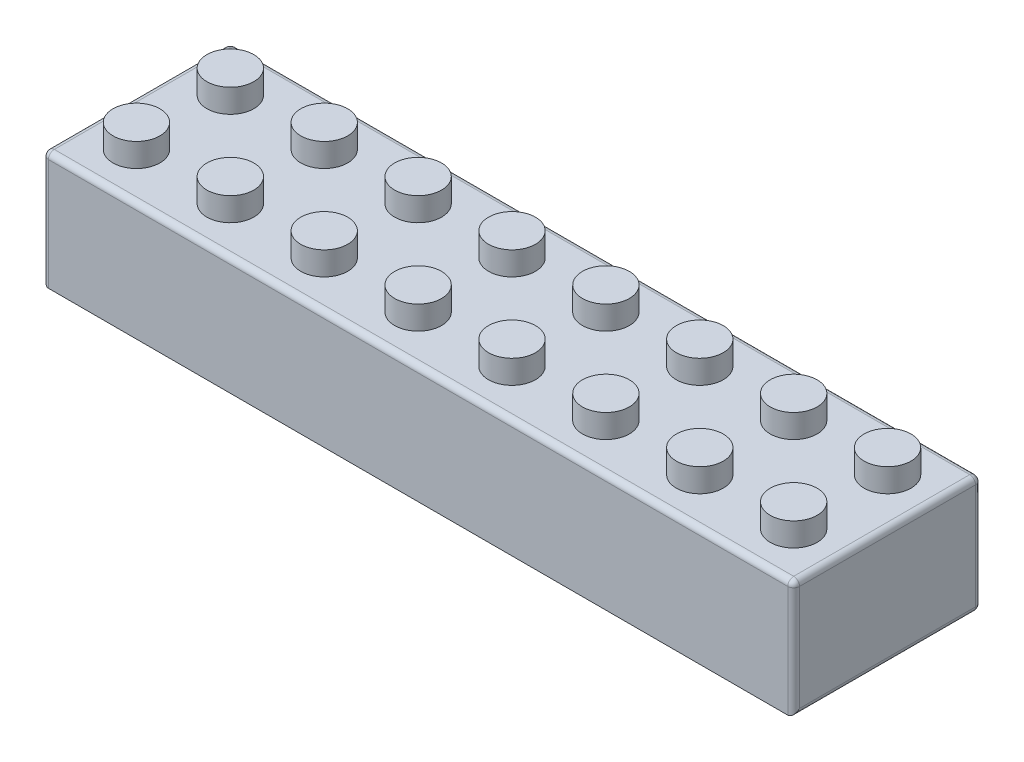
SolidWorks part; units mm, degrees
ref_plane "Front Plane" through (0, 0, 0) normal (0, 0, 1) x (1, 0, 0)
ref_plane "Top Plane" through (0, 0, 0) normal (0, 1, 0) x (1, 0, 0)
ref_plane "Right Plane" through (0, 0, 0) normal (1, 0, 0) x (0, 0, -1)
sketch "Sketch1" plane through (0, 0, 0) normal (0, 0, 1) x (1, 0, 0)
  line L1 (-32, 5) -> (32, 5)
  line L2 (-32, 5) -> (-32, -5)
  line L3 (-32, -5) -> (32, -5)
  line L4 (32, 5) -> (32, -5)
  line L5 (-32, 5) -> (32, -5) construction
  line L6 (-32, -5) -> (32, 5) construction
  point P0 (0, 0)
  dimension "D1" = 10
  dimension "D2" = 64
extrude "Boss-Extrude1" add sketch "Sketch1" along normal blind 8 and the other way blind 8
sketch "Sketch2" plane through (0, 5, 0) normal (0, 1, 0) x (1, 0, 0)
  line L0 (32, 8) -> (-32, 8) construction
  line L2 (-32, 8) -> (-32, -8) construction
  circle A0 centre (-28, 4) radius 2
  circle A1 centre (-20, 4) radius 2
  circle A2 centre (-12, 4) radius 2
  circle A3 centre (-4, 4) radius 2
  circle A4 centre (4, 4) radius 2
  circle A5 centre (12, 4) radius 2
  circle A6 centre (20, 4) radius 2
  circle A7 centre (28, 4) radius 2
  circle A8 centre (-20, -4) radius 2
  circle A9 centre (-12, -4) radius 2
  circle A10 centre (-4, -4) radius 2
  circle A11 centre (4, -4) radius 2
  circle A12 centre (12, -4) radius 2
  circle A13 centre (20, -4) radius 2
  circle A14 centre (28, -4) radius 2
  circle A15 centre (-28, -4) radius 2
  dimension "D1" = 4
  dimension "D2" = 4
  dimension "D3" = 4
  dimension "D4" = 8
  dimension "D5" = 2
extrude "Boss-Extrude2" add sketch "Sketch2" along normal blind 2
shell "Shell1" thickness 1 removed face at (0, -5, 0)
sketch "Sketch3" plane through (0, 4, 0) normal (0, -1, 0) x (-1, 0, 0)
  line L0 (32, 8) -> (32, -8) construction
  line L8 (32, -8) -> (-32, -8) construction
  circle A0 centre (24, 0) radius 2.7726
  circle A1 centre (24, 0) radius 3.7726
  point P6 (23.5453, 7)
  point P7 (23.6495, 8)
  point P8 (23.962, 8)
  dimension "D1" = 5.5452
  dimension "D2" = 8
  dimension "D3" = 8
extrude "Boss-Extrude3" add sketch "Sketch3" along normal blind 9
fillet "Fillet1" radius 0.5 12 edges at (0, -5, 7) (32, -5, 0) (0, -5, -8) (-32, -5, 0) (-32, 5, 0) (0, 5, -8) (0, 5, 8) (32, 5, 0) (32, 0, -8) (32, 0, 8) (-32, 0, -8) (-32, 0, 8)
